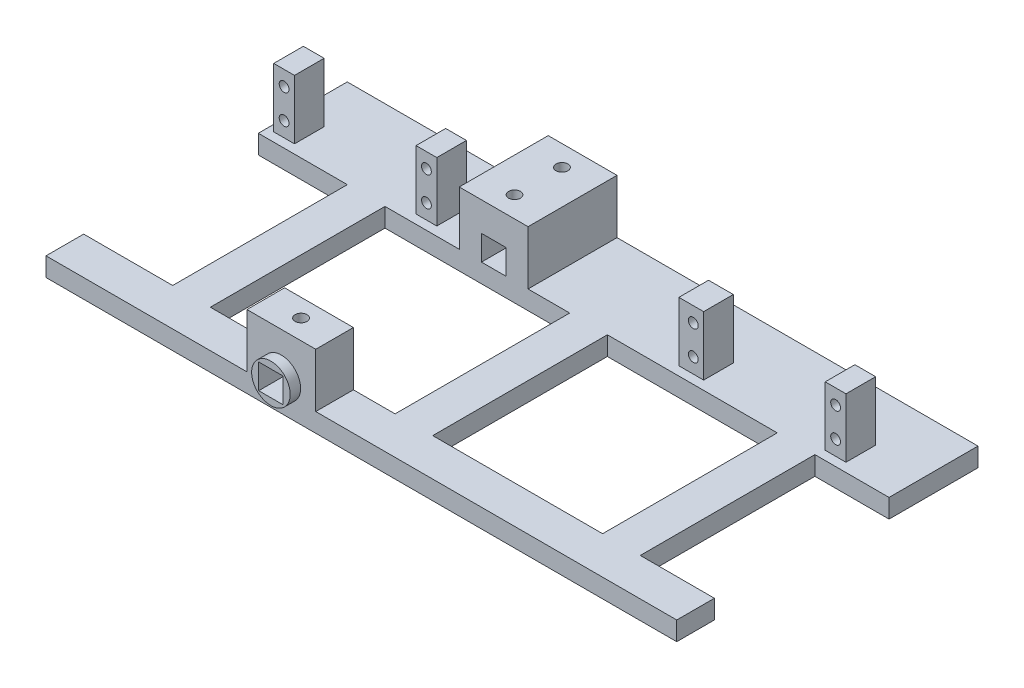
SolidWorks part; units mm, degrees
ref_plane "Front" through (0, 0, 0) normal (0, 0, 1) x (1, 0, 0)
ref_plane "Top" through (0, 0, 0) normal (0, 1, 0) x (1, 0, 0)
ref_plane "Right" through (0, 0, 0) normal (1, 0, 0) x (0, 0, -1)
sketch "Sketch1" plane through (0, 0, 0) normal (0, 1, 0) x (1, 0, 0)
  line L0 (0, 71.6) -> (212.725, 71.6)
  line L1 (0, 0) -> (212.725, 0)
  line L2 (0, 0) -> (0, 101.6)
  line L3 (0, 101.6) -> (212.725, 101.6)
  line L4 (212.725, 0) -> (212.725, 101.6)
  line L5 (0, 12.7) -> (212.725, 12.7)
  line L6 (117.725, 71.6) -> (117.725, 12.7)
  line L7 (187.725, 71.6) -> (187.725, 12.7)
  line L8 (187.725, 12.7) -> (175.025, 12.7)
  line L9 (175.025, 12.7) -> (175.025, 71.6)
  line L10 (175.025, 71.6) -> (105.025, 71.6)
  line L11 (105.025, 71.6) -> (105.025, 12.7)
  line L12 (105.025, 12.7) -> (30.025, 12.7)
  line L13 (30.025, 12.7) -> (30.025, 71.6)
  line L14 (30.025, 71.6) -> (42.725, 71.6)
  line L15 (42.725, 71.6) -> (42.725, 12.7)
  point P21 (42.725, 42.15)
  dimension "D1" = 212.725
  dimension "D2" = 101.6
  dimension "D3" = 30
  dimension "D4" = 12.7
  dimension "D5" = 12.7
  dimension "D6" = 12.7
  dimension "D7" = 12.7
  dimension "D8" = 25
  dimension "D9" = 95
  dimension "D10" = 170
extrude "Boss-Extrude1" add sketch "Sketch1" along normal blind 6.35 contours L0 L4 L3 L2 | L15 L0 L13 L5 | L0 L11 L5 L6 | L9 L5 L7 L0 | L5 L2 L1 L4 L12 region at (106.3625, 0, -86.6) region at (36.375, 0, -42.15) region at (106.3625, 0, -6.35) region at (111.375, 0, -42.15) region at (181.375, 0, -42.15)
sketch "Sketch2" plane through (0, 0, -101.6) normal (0, 0, -1) x (-1, 0, 0)
  line L0 (0, 6.35) -> (63.5, 38.1)
  line L1 (63.5, 38.1) -> (63.5, 25.4)
  line L2 (63.5, 25.4) -> (0, 0)
  line L3 (63.5, 38.1) -> (88.9, 38.1)
  line L4 (88.9, 38.1) -> (88.9, 25.4)
  line L5 (88.9, 25.4) -> (63.5, 25.4)
  line L7 (-212.725, 0) -> (0, 0)
  line L8 (0, 0) -> (0, 6.35)
  line L9 (0, 6.35) -> (-212.725, 6.35)
  line L10 (-212.725, 6.35) -> (-212.725, 0)
  line L11 (-212.725, 0) -> (0, 0)
  line L13 (0, 6.35) -> (-212.725, 6.35)
  line L14 (-212.725, 6.35) -> (-212.725, 0)
  line M3 (0, 0) -> (0, 6.35)
  dimension "D1" = 12.7
  dimension "D2" = 63.5
  dimension "D3" = 25.4
  dimension "D5" = 25.4
  dimension "D4" = 0
extrude "Boss-Extrude2" [suppressed] add sketch "Sketch2" against normal blind 30 contours L2 L1 L0 M3 | L5 L4 L3 L1
ref_plane "Plane1" through (0, 0, -50.8) normal (0, 0, -1) x (-1, 0, 0)
sketch "Sketch4" plane through (0, 0, 0) normal (0, 0, 1) x (1, 0, 0)
  line L0 (0, 6.35) -> (-63.5, 38.1)
  line L1 (-63.5, 38.1) -> (-63.5, 25.4)
  line L2 (-63.5, 25.4) -> (0, 0)
  line L3 (0, 6.35) -> (0, 0)
  line L4 (-63.5, 38.1) -> (-88.9, 38.1)
  line L5 (-88.9, 38.1) -> (-88.9, 25.4)
  line L6 (-88.9, 25.4) -> (-63.5, 25.4)
  line M5 (0, 6.35) -> (0, 0)
  dimension "D1" = 12.7
  dimension "D2" = 63.5
  dimension "D3" = 25.4
  dimension "D4" = 25.4
extrude "Boss-Extrude3" [suppressed] add sketch "Sketch4" against normal blind 12.7 contours L5 L6 L1 L4 | L1 L2 L0 M5
sketch "Sketch5" [suppressed] plane through (0, 0, -71.6) normal (0, 0, 1) x (1, 0, 0)
  line L6 (-76.2, 38.1) -> (-76.2, 25.4)
  line L7 (-63.5, 38.1) -> (-88.9, 38.1) construction
  line L8 (-88.9, 25.4) -> (-63.5, 25.4) construction
  line L9 (-76.2, 25.4) -> (-88.9, 25.4)
  line L10 (-88.9, 25.4) -> (-88.9, 38.1)
  line L11 (-88.9, 38.1) -> (-76.2, 38.1)
extrude "Boss-Extrude4" [suppressed] add sketch "Sketch5" along normal up to next
sketch "Sketch6" plane through (0, 6.35, 0) normal (0, 1, 0) x (1, 0, 0)
  line L0 (212.725, 74.6) -> (174.5417, 74.6)
  line L1 (212.725, 71.6) -> (212.725, 101.6) construction
  line L2 (187.725, 71.6) -> (212.725, 71.6) construction
  line L3 (188.2, 74.6) -> (188.2, 84.6)
  line L4 (188.2, 84.6) -> (195.2, 84.6)
  line L5 (195.2, 84.6) -> (195.2, 74.6)
  line L6 (147.2, 74.6) -> (147.2, 84.6)
  line L7 (147.2, 84.6) -> (130.5, 84.6)
  line L8 (130.5, 84.6) -> (130.5, 74.6)
  line L9 (130.5, 74.6) -> (147.2, 74.6)
  line L10 (138.85, 74.6) -> (138.85, 84.6)
  line L11 (89.5, 84.6) -> (82.5, 84.6)
  line L12 (82.5, 84.6) -> (82.5, 74.6)
  line L13 (64.975, 74.6) -> (103.1583, 74.6)
  line L14 (89.5, 74.6) -> (89.5, 84.6)
  line L15 (50.2, 74.6) -> (50.2, 84.6)
  line L16 (74.725, 74.6) -> (36.5417, 74.6)
  line L17 (57.2, 84.6) -> (57.2, 74.6)
  line L18 (50.2, 84.6) -> (57.2, 84.6)
  line L19 (9.2, 74.6) -> (9.2, 84.6)
  line L20 (-15.325, 74.6) -> (22.8583, 74.6)
  line L21 (2.2, 84.6) -> (2.2, 74.6)
  line L22 (9.2, 84.6) -> (2.2, 84.6)
  line L23 (117.725, 71.6) -> (117.725, 12.7) construction
  point P6 (200.225, 71.6)
  point P15 (188.2, 79.6)
  dimension "D1" = 3
  dimension "D2" = 7
  dimension "D3" = 10
  dimension "D4" = 10
  dimension "D5" = 16.7
  dimension "D6" = 41
  dimension "D7" = 24.525
  dimension "D8" = 0
  dimension "D9" = 49.35
  dimension "D12" = 41
  dimension "D13" = 60.525
  dimension "D10" = 2
  dimension "D11" = 2
extrude "Boss-Extrude5" add sketch "Sketch6" along normal blind 20 contours L8 L9 L6 L7 | L5 L4 L3 L0 | L18 L15 L16 L17 | L19 L22 L21 L20 region at (191.7, 6.35, -79.6) region at (143.025, 6.35, -79.6) region at (53.7, 6.35, -79.6) region at (5.7, 6.35, -79.6)
fillet "Fillet8" [suppressed] radius 8
sketch "Sketch9" plane through (0, 0, -101.6) normal (0, 0, -1) x (-1, 0, 0)
  line L0 (-83.475, 6.35) -> (-83.475, 14.75)
  line L1 (0, 6.35) -> (-212.725, 6.35) construction
  line L2 (-83.475, 14.75) -> (-75.275, 14.75)
  line L3 (-75.275, 14.75) -> (-75.275, 6.35)
  line L4 (-90.975, 6.35) -> (-90.975, 24.55)
  line L5 (-90.975, 24.55) -> (-67.775, 24.55)
  line L6 (-67.775, 24.55) -> (-67.775, 6.35)
  line L7 (-212.725, 6.35) -> (-212.725, 0) construction
  line L8 (-90.975, 6.35) -> (-83.475, 6.35)
  line L9 (-67.775, 6.35) -> (-75.275, 6.35)
  point P10 (-79.375, 14.75)
  dimension "D1" = 8.2
  dimension "D2" = 8.4
  dimension "D3" = 133.35
  dimension "D4" = 9.8
  dimension "D5" = 7.5
  dimension "D6" = 7.5
sketch "Sketch7" plane through (0, 0, -74.6) normal (0, 0, 1) x (1, 0, 0)
  line L0 (147.2, 16.35) -> (188.2, 16.35)
  line L1 (147.2, 26.35) -> (147.2, 6.35) construction
  line L2 (188.2, 26.35) -> (188.2, 6.35) construction
  line L3 (143.7, 16.35) -> (191.7, 16.35)
  line L4 (143.7, 21.3) -> (143.7, 11.4)
  line L5 (191.7, 21.3) -> (191.7, 11.4)
  circle A0 centre (143.7, 21.3) radius 1.65
  circle A1 centre (143.7, 11.4) radius 1.65
  circle A2 centre (191.7, 21.3) radius 1.65
  circle A3 centre (191.7, 11.4) radius 1.65
  circle A4 centre (86, 21.3) radius 1.65
  circle A5 centre (86, 11.4) radius 1.65
  circle A6 centre (134, 21.3) radius 1.65
  circle A7 centre (134, 11.4) radius 1.65
  circle A8 centre (5.7, 21.3) radius 1.65
  circle A9 centre (5.7, 11.4) radius 1.65
  circle A10 centre (53.7, 11.4) radius 1.65
  circle A11 centre (53.7, 21.3) radius 1.65
  point P9 (167.7, 16.35)
  point P11 (143.7, 16.35)
  point P15 (191.7, 16.35)
  dimension "D4" = 2
  dimension "D1" = 48
  dimension "D2" = 9.9
  dimension "D3" = 9.9
  dimension "D5" = 2
extrude "Cut-Extrude1" cut sketch "Sketch7" against normal through all contours A8 | A11 | A4 | A5 | A6 | A7 | A0 | A1 | A2 | A3 | A9 | A10 region at (190.5663, 22.4337, -74.6) region at (192.8337, 12.5337, -74.6) region at (144.8337, 12.5337, -74.6) region at (142.5663, 22.4337, -74.6) region at (86, 21.3, -74.6) region at (86, 11.4, -74.6) region at (134, 21.3, -74.6) region at (134, 11.4, -74.6) region at (5.7, 21.3, -74.6) region at (53.7, 21.3, -74.6)
extrude "Boss-Extrude6" add sketch "Sketch9" against normal blind 30
ref_plane "Plane2" through (0, 0, -50.8) normal (0, 0, -1) x (-1, 0, 0)
mirror "Mirror1" about plane through (0, 0, -50.8) normal (0, 0, -1) of "Boss-Extrude6"
sketch "Sketch10" plane through (0, 6.35, 0) normal (0, -1, 0) x (-1, 0, 0)
  line L1 (-90.975, 12.7) -> (-67.775, 12.7)
  line L2 (-90.975, 12.7) -> (-90.975, 30)
  line L3 (-90.975, 30) -> (-67.775, 30)
  line L4 (-67.775, 12.7) -> (-67.775, 30)
extrude "Cut-Extrude2" cut sketch "Sketch10" against normal through all
sketch "Sketch11" plane through (0, 0, -101.6) normal (0, 0, -1) x (-1, 0, 0)
  line L0 (-79.375, 14.75) -> (-79.375, 6.35)
  line L1 (-83.475, 14.75) -> (-75.275, 14.75) construction
  line L2 (-75.275, 6.35) -> (-83.475, 6.35) construction
  circle A0 centre (-79.375, 10.55) radius 6.5
  line M1 (-75.275, 6.35) -> (-83.475, 6.35)
  line M2 (-83.475, 6.35) -> (-83.475, 14.75)
  line M3 (-83.475, 14.75) -> (-75.275, 14.75)
  line M4 (-75.275, 14.75) -> (-75.275, 6.35)
extrude "Boss-Extrude7" add sketch "Sketch11" along normal blind 2 contours A0 M4 M1 M2 M3 region at (85.6912, 10.55, -101.6)
sketch "Sketch12" plane through (0, 0, -103.6) normal (0, 0, -1) x (-1, 0, 0)
  line L0 (-79.375, 14.75) -> (-79.375, 6.35)
  line L1 (-83.475, 14.75) -> (-75.275, 14.75) construction
  line L2 (-75.275, 6.35) -> (-83.475, 6.35) construction
  circle A0 centre (-79.375, 10.55) radius 6.5
  line M1 (-75.275, 14.75) -> (-75.275, 6.35)
  line M2 (-75.275, 6.35) -> (-83.475, 6.35)
  line M3 (-83.475, 6.35) -> (-83.475, 14.75)
  line M4 (-83.475, 14.75) -> (-75.275, 14.75)
extrude "Boss-Extrude8" add sketch "Sketch12" along normal blind 1.525 contours A0 M4 M1 M2 M3 region at (85.6912, 10.55, -103.6)
mirror "Mirror2" about plane through (0, 0, -50.8) normal (0, 0, -1) of "Boss-Extrude7", "Boss-Extrude8"
sketch "Sketch14" plane through (0, 6.35, 0) normal (0, 1, 0) x (1, 0, 0)
  line L0 (90.975, 101.6) -> (90.975, 71.6)
  line L1 (90.975, 71.6) -> (105.025, 71.6)
  line L2 (130.5, 74.6) -> (147.2, 74.6)
  line L3 (147.2, 74.6) -> (138.85, 74.6)
  line L4 (138.85, 74.6) -> (138.85, 71.6)
  line L5 (117.725, 71.6) -> (175.025, 71.6) construction
  line L6 (138.85, 71.6) -> (105.025, 71.6)
  line L7 (138.85, 74.6) -> (138.85, 88.9)
  line L8 (138.85, 88.9) -> (90.975, 88.9)
  line L9 (90.975, 101.6) -> (212.725, 101.6) construction
  line L10 (138.85, 92.6) -> (140.025, 92.6)
  line L11 (130.5, 92.6) -> (147.2, 92.6) construction
  line L12 (140.025, 92.6) -> (140.025, 88.9)
  line L13 (140.025, 84.6) -> (140.025, 74.6) construction
  line L14 (138.85, 88.9) -> (138.85, 92.6)
  dimension "D1" = 12.7
extrude "Cut-Extrude4" [suppressed] cut sketch "Sketch14" along normal through all
sketch "Sketch15" [suppressed] plane through (0, 6.35, 0) normal (0, 1, 0) x (1, 0, 0)
  line L0 (185.675, 84.6) -> (203.2, 84.6)
  line L1 (203.2, 71.6) -> (203.2, 101.6) construction
  line L2 (203.2, 84.6) -> (81.45, 84.6)
  line L3 (81.45, 71.6) -> (81.45, 101.6) construction
  line L4 (81.45, 84.6) -> (81.45, 101.6)
  line L5 (81.45, 101.6) -> (203.2, 101.6)
  line L6 (203.2, 101.6) -> (203.2, 84.6)
  line L7 (57.2, 84.6) -> (55.75, 84.6)
  line L8 (55.75, 71.6) -> (55.75, 74.6) construction
  line L9 (55.75, 84.6) -> (55.75, 101.6)
  line L10 (55.75, 101.6) -> (0, 101.6)
  line L11 (0, 101.6) -> (0, 84.6)
  line L12 (0, 71.6) -> (0, 101.6) construction
  line L13 (0, 84.6) -> (57.2, 84.6)
extrude "Cut-Extrude5" [suppressed] cut sketch "Sketch15" against normal through all
sketch "Sketch17" plane through (0, 24.55, 0) normal (0, 1, 0) x (1, 0, 0)
  line L0 (79.375, 101.6) -> (79.375, 94.6355)
  line L1 (67.775, 101.6) -> (90.975, 101.6) construction
  line L2 (79.375, 94.6355) -> (79.375, 78.6355)
  line L3 (79.375, 78.6355) -> (79.375, 6.6355)
  circle A0 centre (79.375, 6.6355) radius 2
  circle A1 centre (79.375, 78.6355) radius 2
  circle A2 centre (79.375, 94.6355) radius 2
  dimension "D1" = 6.9645
  dimension "D2" = 16
  dimension "D3" = 72
extrude "Cut-Extrude6" cut sketch "Sketch17" against normal through all contours A0 | L2 A1 L3 | L0 A2 L2 | L2 A2 L0 | L3 A1 L2 region at (80.2238, 24.55, -94.6355) region at (80.7492, 24.55, -8.0097) region at (80.2238, 24.55, -78.6355) region at (78.5262, 24.55, -78.6355) region at (78.5262, 24.55, -94.6355)
fillet "Fillet9" [suppressed] radius 5
fillet "Fillet10" [suppressed] radius 3
fillet "Fillet11" [suppressed] radius 2
fillet "Fillet12" [suppressed] radius 2
chamfer "Chamfer1" [suppressed] distance 10 angle 45
